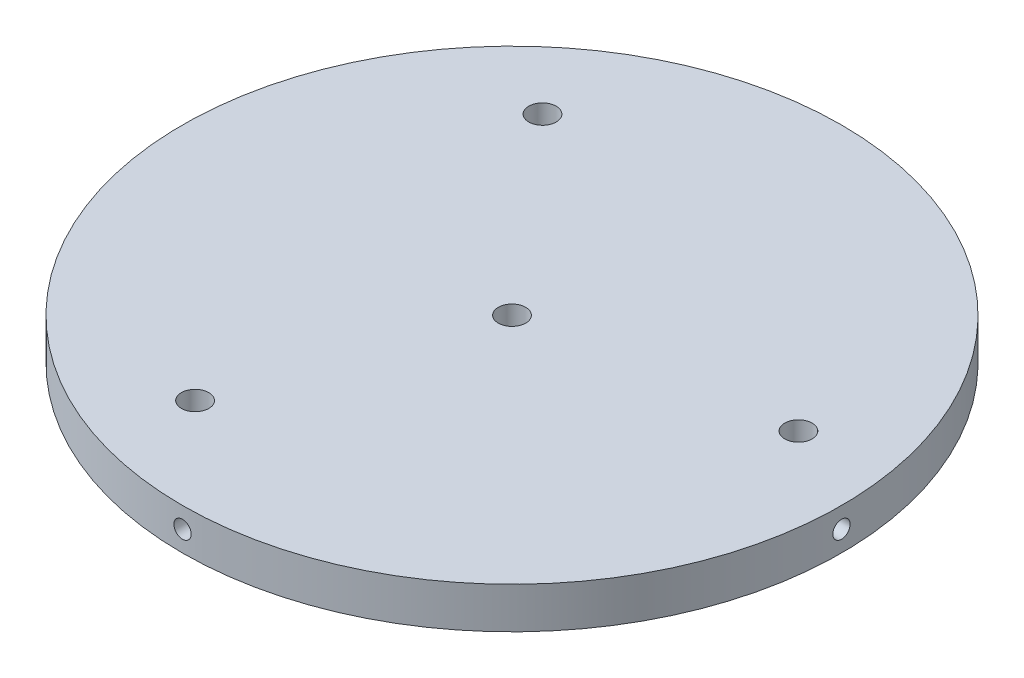
SolidWorks part; units mm, degrees
material "6061-T6 (SS)"
ref_plane "Front Plane" through (0, 0, 0) normal (0, 0, 1) x (1, 0, 0)
ref_plane "Top Plane" through (0, 0, 0) normal (0, 1, 0) x (1, 0, 0)
ref_plane "Right Plane" through (0, 0, 0) normal (1, 0, 0) x (0, 0, -1)
sketch "Sketch1" plane through (0, 0, 0) normal (0, 1, 0) x (1, 0, 0)
  line L0 (0, 0) -> (-50.3682, 60.0265)
  line L1 (0, 0) -> (50.3682, 60.0265)
  line L2 (0, 0) -> (0, 72.1431) construction
  circle A0 centre (0, 0) radius 78.359
  circle A1 centre (0, 0) radius 76.1746
  circle A2 centre (0, 0) radius 76.1746
  dimension "D1" = 156.718
  dimension "D2" = 152.3492
  dimension "D3" = 152.3492
  dimension "D4" = 80
extrude "Boss-Extrude1" add sketch "Sketch1" along normal blind 25.4 contours L2 A2 L1 A0 | L2 A1 L1 A2 | L2 A2 L1 A1 | L2 A0 L1 A2 | A2 L2 A1 L0 | A0 L2 A2 L0 | A2 L2 A0 L0 | A1 L2 A2 L0 region at (0, 0, 13.3592) region at (-23.5316, 0, -29.974) region at (-33.0764, 0, 70.9325) region at (-48.8794, 0, -59.85)
ref_plane "Plane1" through (0, 12.7, 0) normal (0, 1, 0) x (1, 0, 0)
sketch "Sketch6" plane through (0, 25.4, 0) normal (0, 1, 0) x (1, 0, 0)
  circle A0 centre (0, 0) radius 76.1746
  dimension "D1" = 152.3492
extrude "Boss-Extrude5" add sketch "Sketch6" along normal blind 9.525
sketch "Sketch7" plane through (0, 0, 0) normal (0, -1, 0) x (1, 0, 0)
  circle A0 centre (0, 0) radius 76.1746
  dimension "D1" = 152.3492
extrude "Boss-Extrude6" add sketch "Sketch7" along normal blind 9.525
sketch "Sketch8" plane through (0, -9.525, 0) normal (0, -1, 0) x (1, 0, 0)
  circle A0 centre (0, 0) radius 73.025
  dimension "D1" = 146.05
extrude "Cut-Extrude5" cut sketch "Sketch8" against normal up to surface (34.925 mm away) up to face at (0, 25.4, 76.1746)
ref_plane "Plane2" through (0, 0, -76.1746) normal (0, 0, -1) x (-1, 0, 0)
ref_plane "Plane5" through (0, 25.4, 0) normal (0, 1, 0) x (1, 0, 0)
ref_axis "Axis1" through (0, 0, 0) along (0, 1, 0)
sketch "Sketch3" plane through (0, 0, -76.1746) normal (0, 0, -1) x (-1, 0, 0)
  line L4 (76.1746, 0) -> (-76.1746, 0)
  line L5 (-76.1746, -9.525) -> (76.1746, -9.525)
  line L6 (76.1746, 25.4) -> (-76.1746, 25.4)
  line L7 (76.1746, 34.925) -> (-76.1746, 34.925)
  line L8 (0, 34.925) -> (0, 25.4) construction
  line L9 (0, 0) -> (0, -9.525) construction
  circle A0 centre (0, 30.1625) radius 2
  circle A1 centre (0, -4.7625) radius 2
  point P12 (0, 30.1625)
  point P13 (0, -4.7625)
  point P14 (-77.5445, 179.1871)
  dimension "D1" = 4
extrude "Cut-Extrude2" cut sketch "Sketch3" against normal blind 9.525 contours L8 A0 | L8 A0 | L9 A1 | L9 A1 region at (0, 30.1625, -76.1746) region at (0, -4.7625, -76.1746)
extrude "Cut-Extrude3" cut sketch "Sketch1<7>" against normal blind 9.525 from surface contours L2 A1 L1 A2 | A1 L2 A2 L0 | A2 L2 A0 L0 | L2 A2 L1 A0 region at (-23.5316, 0, -29.974) region at (-48.8794, 0, -59.85) starting at plane "Plane5"
sketch "Sketch1<7>" plane through (0, 0, 0) normal (0, 1, 0) x (1, 0, 0) same geometry as "Sketch1"
pattern_circular "CirPattern2" count 3 over 360 about axis through (0, 0, 0) along (0, 1, 0) of "Cut-Extrude3"
ref_plane "Plane3" through (0, 34.925, 0) normal (0, 1, 0) x (1, 0, 0)
sketch "Sketch4" plane through (0, 34.925, 0) normal (0, 1, 0) x (1, 0, 0)
  circle A0 centre (0, 0) radius 73.025
  dimension "D1" = 146.05
extrude "Boss-Extrude4" add sketch "Sketch4" against normal blind 9.525
pattern_circular "CirPattern3" count 4 over 360 about axis through (0, 0, 0) along (0, 1, 0) of "Cut-Extrude2"
sketch "Sketch9" plane through (0, 34.925, 0) normal (0, 1, 0) x (1, 0, 0)
  line L0 (0, 0) -> (-26.8004, -73.6334) construction
  circle A0 centre (0, 0) radius 3.175
  circle A1 centre (-19.5465, -53.7034) radius 3.175
  circle A2 centre (-36.7353, 43.7794) radius 3.175
  circle A3 centre (56.2818, 9.924) radius 3.175
  point P15 (0, 0)
  dimension "D1" = 6.35
  dimension "D2" = 6.35
  dimension "D3" = 57.15
  dimension "D5" = 3
extrude "Cut-Extrude6" cut sketch "Sketch9" against normal through all
sketch "Sketch10" plane through (0, 25.4, 0) normal (0, 1, 0) x (1, 0, 0)
  circle A0 centre (0, 0) radius 82.3228
extrude "Cut-Extrude7" cut sketch "Sketch10" against normal through all
equation "\"AB_Coupler_OD_Length\"= 1in"
equation "\"AB_Coupling_Section_Length\"= 0.375in"
equation "\"AB_Coupler_Length\"= \"AB_Coupler_OD_Length\" + \"AB_Coupling_Section_Length\" * 2"
equation "\"Cutout_Angle\" = 80"
equation "\"AB_Coupler_Num_Screws\"= 6"
equation "\"Num_Cutouts\" = 3"
equation "\"AB_Coupler_OD\"= 6.17in"
equation "\"AB_Coupler_ID\"= 5.75in"
equation "\"AB_Coupler_Surface_Diameter\"= 5.998in"
equation "\"D2@Sketch1\"=\"Bodytube_ID\""
equation "\"AB_Coupling_Screw_Diameter\"= 0.1065in"
equation "\"Aft_Section_Length\"= 39in"
equation "\"Aft_Lower_Length\"= 22in"
equation "\"Aft_Upper_Length\"= \"Aft_Section_Length\" - \"Aft_Lower_Length\" - \"AB_Coupler_OD_Length\""
equation "\"Mid_Coupler_Length\"= 13in"
equation "\"Lead_Screw_Dist\" = 2.25in"
equation "\"Lead_Screw_Diam\" = (27/64)*1in"
equation "\"Lead_Screw_Length\" = (\"Mid_Coupler_Length\" + 2*0.375in + 2*0.5in)"
equation "\"Bodytube_OD\" = 6.17in"
equation "\"Paddle_Pin_Offset\" = .25in"
equation "\"Bodytube_ID\" = 5.998in"
equation "\"Paddle_Pin_Radius\" = 2.25in"
equation "\"D1@Sketch4\"=\"AB_Coupler_ID\""
equation "\"D1@Sketch6\"=\"AB_Coupler_Surface_Diameter\""
equation "\"D1@Boss-Extrude5\"=\"AB_Coupling_Section_Length\""
equation "\"D1@Sketch7\"=\"AB_Coupler_Surface_Diameter\""
equation "\"D1@Boss-Extrude6\"=\"AB_Coupling_Section_Length\""
equation "\"D1@Sketch8\"=\"AB_Coupler_ID\""
equation "\"D3@Sketch9\"=\"Paddle_Pin_Radius\""
